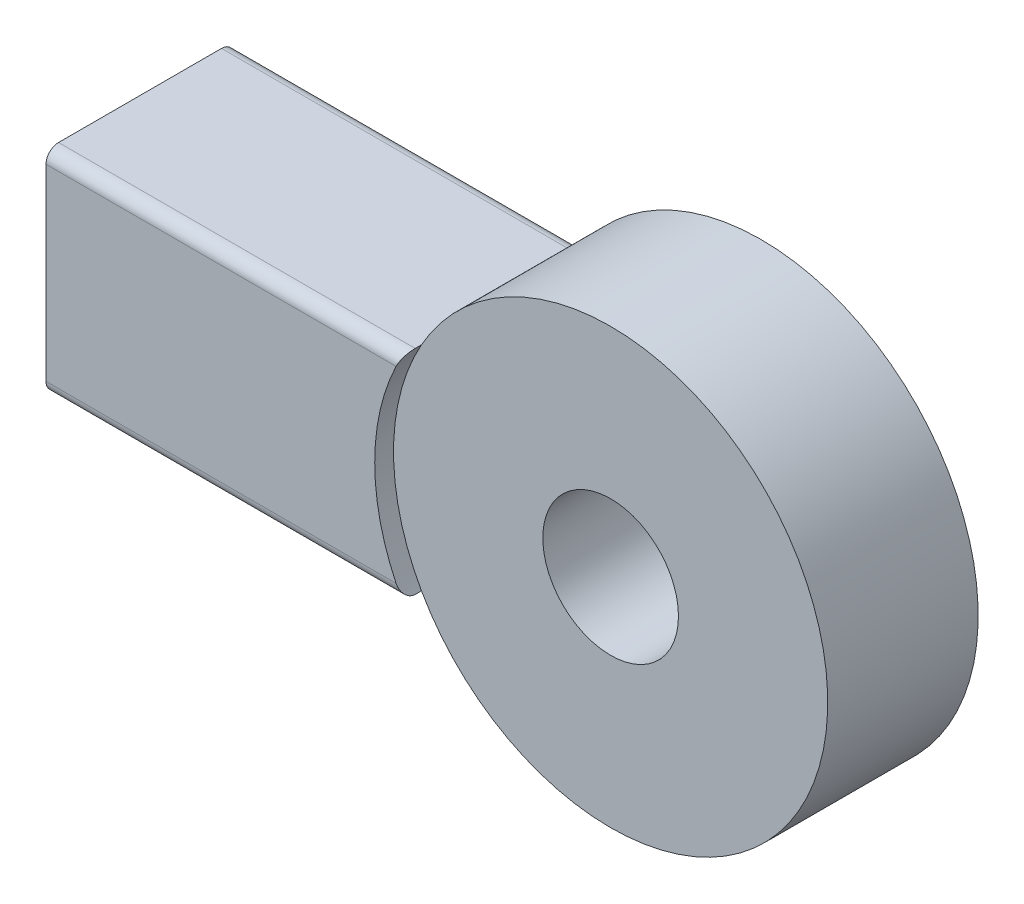
SolidWorks part; units mm, degrees
ref_plane "Front" through (0, 0, 0) normal (0, 0, 1) x (1, 0, 0)
ref_plane "Top" through (0, 0, 0) normal (0, 1, 0) x (1, 0, 0)
ref_plane "Right" through (0, 0, 0) normal (1, 0, 0) x (0, 0, -1)
sketch "Sketch1" plane through (0, 0, 0) normal (0, 0, 1) x (1, 0, 0)
  line L0 (0, 0) -> (-29.3153, 0) construction
  line L1 (-15.0905, -8.4982) -> (-43.54, -8.4982)
  line L3 (-15.0905, 8.4982) -> (-43.54, 8.4982)
  line L4 (-43.54, -8.4982) -> (-43.54, 8.4982)
  line L5 (-15.0905, -8.4982) -> (-43.54, 8.4982) construction
  line L6 (-15.0905, 8.4982) -> (-43.54, -8.4982) construction
  circle A0 centre (0, 0) radius 17.3189
  circle A1 centre (0, 0) radius 5.4117
  arc A2 (-6.5519, 16.0317) -> (16.8464, 4.0177) centre (0, 0) ccw construction
  circle A3 centre (0, 0) radius 5.4117 construction
  point P3 (-29.3153, 0)
extrude "Boss-Extrude1" add sketch "Sketch1" along normal mid plane 12 contours A0 region at (-16.829, 0, 0)
extrude "Boss-Extrude2" add sketch "Sketch1<3>" along normal mid plane 15 contours A0 L3 L4 L1 region at (-30.0601, 0, 0)
sketch "Sketch1<3>" plane through (0, 0, 0) normal (0, 0, 1) x (1, 0, 0) same geometry as "Sketch1"
sketch "Sketch2" plane through (-43.54, 0, 0) normal (-1, 0, 0) x (0, 0, 1)
  line L8 (-5.5, 6.4982) -> (-5.5, -6.4982)
  line L9 (-5.5, -6.4982) -> (5.5, -6.4982)
  line L10 (5.5, -6.4982) -> (5.5, 6.4982)
  line L11 (5.5, 6.4982) -> (-5.5, 6.4982)
  line L12 (-5.5, 6.4982) -> (-5.5, -6.4982)
  line L13 (-5.5, -6.4982) -> (5.5, -6.4982)
  line L14 (5.5, -6.4982) -> (5.5, 6.4982)
  line L15 (5.5, 6.4982) -> (-5.5, 6.4982)
  dimension "D1" = 2
extrude "Cut-Extrude1" cut sketch "Sketch2" against normal blind 26
fillet "Fillet1" radius 1 4 edges at (-29.3153, 8.4982, -7.5) (-29.3153, -8.4982, -7.5) (-29.3153, 8.4982, 7.5) (-29.3153, -8.4982, 7.5)
